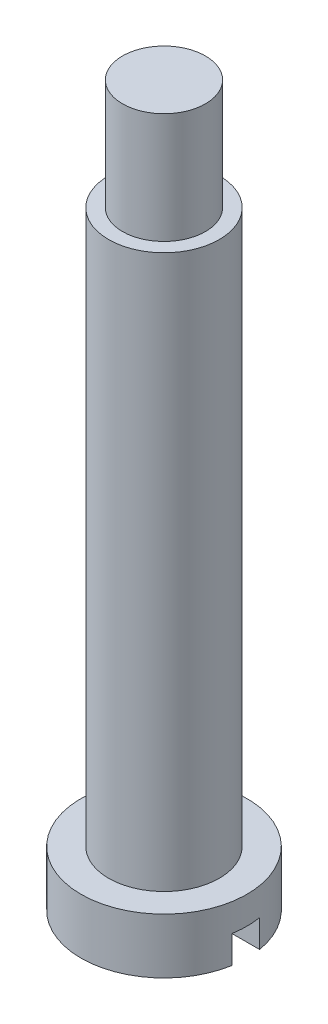
SolidWorks part; units mm, degrees
ref_plane "前视基准面" through (0, 0, 0) normal (0, 0, 1) x (1, 0, 0)
ref_plane "上视基准面" through (0, 0, 0) normal (0, 1, 0) x (1, 0, 0)
ref_plane "右视基准面" through (0, 0, 0) normal (1, 0, 0) x (0, 0, -1)
other "Configuration Table"
sketch "草图1" plane through (0, 0, 0) normal (0, 1, 0) x (1, 0, 0)
  circle A0 centre (0, 0) radius 3
  dimension "D1" = 6
extrude "凸台-拉伸1" add sketch "草图1" against normal blind 2
sketch "草图2" plane through (0, 0, 0) normal (0, 1, 0) x (1, 0, 0)
  circle A0 centre (0, 0) radius 2
  dimension "D1" = 4
extrude "凸台-拉伸2" add sketch "草图2" along normal blind 20 contours A0
sketch "草图3" plane through (0, 20, 0) normal (0, 1, 0) x (1, 0, 0)
  circle A0 centre (0, 0) radius 1.5
  dimension "D1" = 3
extrude "凸台-拉伸3" add sketch "草图3" along normal blind 4
sketch "草图4" plane through (0, -2, 0) normal (0, -1, 0) x (1, 0, 0)
  line L0 (-3, 0) -> (3, 0)
  circle A0 centre (0, 0) radius 3 construction
extrude "切除-拉伸-薄壁1" cut sketch "草图4" against normal blind 1 and the other way through all thin thin type mid plane wall 1
ref_axis "基准轴1" through (0, 31.8772, 0) along (0, -1, 0)
